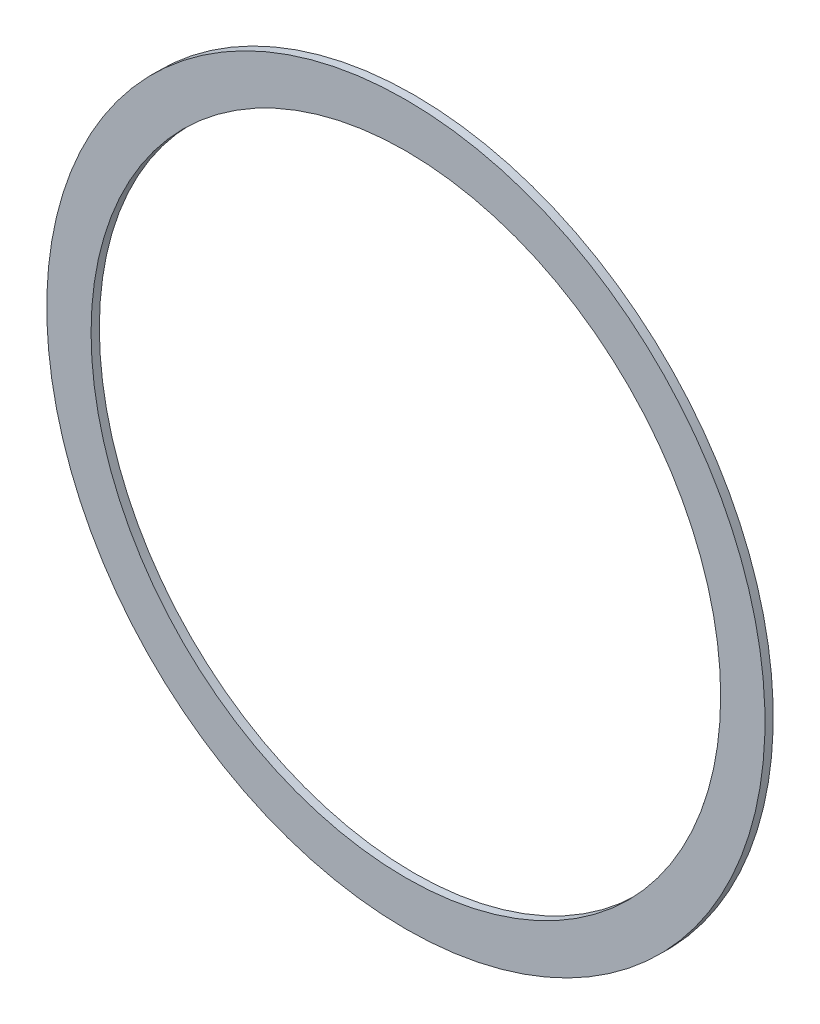
SolidWorks part; units mm, degrees
material "Balsa"
ref_plane "Front Plane" through (0, 0, 0) normal (0, 0, 1) x (1, 0, 0)
ref_plane "Top Plane" through (0, 0, 0) normal (0, 1, 0) x (1, 0, 0)
ref_plane "Right Plane" through (0, 0, 0) normal (1, 0, 0) x (0, 0, -1)
sketch "Sketch1" plane through (0, 0, 0) normal (0, 0, 1) x (1, 0, 0)
  line L0 (0, 0) -> (0, 499.9473) construction
  line L1 (0, -114.7984) -> (0, -129.4545) construction
  line L2 (0, -374.4718) -> (0, 404.2655) construction
  line L3 (-1.651, 142.9921) -> (-1.651, 150.6121) construction
  line L4 (1.651, 142.9921) -> (1.651, 150.6121) construction
  line L5 (-1.651, 142.9921) -> (1.651, 142.9921) construction
  line L6 (136.2041, -53.806) -> (0.0002, 24.7625) construction
  line L7 (-136.2076, -53.7991) -> (0.0002, 24.7625) construction
  line L8 (136.2041, -53.806) -> (0.0002, 24.7625) construction
  line L9 (-136.2076, -53.7991) -> (0.0002, 24.7625) construction
  line L10 (-125.0584, -45.4626) -> (-118.4576, -41.6554) construction
  line L11 (-123.6259, -48.4483) -> (-116.8078, -44.5157) construction
  line L12 (-118.4576, -41.6554) -> (-116.8078, -44.5157) construction
  line L13 (-124.1455, -48.7479) -> (-123.6847, -48.4822) construction
  line L14 (-123.6847, -48.4822) -> (-123.6259, -48.4483) construction
  line L15 (-125.7952, -45.8876) -> (-125.1113, -45.4931) construction
  line L16 (-125.1113, -45.4931) -> (-125.0584, -45.4626) construction
  line L17 (125.4797, -45.7137) -> (125.1075, -45.499) construction
  line L18 (123.8298, -48.5739) -> (123.6807, -48.488) construction
  line L19 (117.0223, -44.647) -> (118.6722, -41.7868) construction
  line L20 (123.6807, -48.488) -> (123.6228, -48.4545) construction
  line L21 (123.6228, -48.4545) -> (117.0223, -44.647) construction
  line L22 (125.1075, -45.499) -> (125.0554, -45.4689) construction
  line L23 (125.0554, -45.4689) -> (118.6722, -41.7868) construction
  line L24 (-115.3206, -47.981) -> (-121.8597, -51.7592)
  line L25 (-113.7312, -50.732) -> (-120.2754, -54.5131)
  line L26 (-113.7312, -50.732) -> (-120.2754, -54.5131) construction
  line L27 (-115.3206, -47.981) -> (-121.8597, -51.7592) construction
  line L28 (-115.4206, -47.9666) -> (-121.9445, -51.7361) construction
  line L29 (-120.2754, -54.5131) -> (-115.3206, -47.981) construction
  line L30 (-117.798, -51.2471) -> (-122.1124, -53.7399) construction
  line L31 (-113.7686, -50.8257) -> (-120.3665, -54.6379) construction
  line L32 (-115.4206, -47.9666) -> (-113.7686, -50.8257) construction
  line L33 (113.7316, -50.7396) -> (129.9098, -60.0883)
  line L34 (115.3212, -47.9888) -> (131.505, -57.3407)
  line L35 (129.9098, -60.0883) -> (131.505, -57.3407)
  line L36 (129.9098, -60.0883) -> (131.505, -57.3407) construction
  line L37 (115.3212, -47.9888) -> (131.505, -57.3407) construction
  line L38 (113.7316, -50.7396) -> (129.9098, -60.0883) construction
  line L39 (129.9098, -60.0883) -> (115.3212, -47.9888) construction
  line L40 (122.6155, -54.0385) -> (101.8722, -42.0519) construction
  line L41 (120.3631, -54.6438) -> (113.7655, -50.8313)
  line L42 (122.0152, -51.7848) -> (122.0057, -51.7794) construction
  line L43 (113.7655, -50.8313) -> (115.4176, -47.9723)
  line L44 (122.0057, -51.7794) -> (121.9413, -51.7421) construction
  line L45 (121.9413, -51.7421) -> (115.4176, -47.9723)
  line L48 (-115.3206, -47.981) -> (-113.7312, -50.732)
  line L49 (-115.3206, -47.981) -> (-113.7312, -50.732) construction
  line L51 (113.7316, -50.7396) -> (115.3212, -47.9888)
  line L52 (113.7316, -50.7396) -> (115.3212, -47.9888) construction
  arc A0 (-1.651, 150.6121) -> (-125.0584, -45.4626) centre (0, 12.7) ccw
  circle A1 centre (0, 12.7) radius 120.904
  arc A2 (0, 150.622) -> (-1.651, 150.6121) centre (0, 12.7) ccw
  circle A3 centre (0, 12.7) radius 137.922 construction
  arc A4 (1.651, 150.6121) -> (0, 150.622) centre (0, 12.7) ccw
  arc A5 (-124.3508, -46.9604) -> (-123.6259, -48.4483) centre (0, 12.7) ccw
  arc A6 (-123.6259, -48.4483) -> (-121.9445, -51.7361) centre (0, 12.7) ccw
  arc A7 (-125.0584, -45.4626) -> (-124.3508, -46.9604) centre (0, 12.7) ccw
  arc A8 (124.3477, -46.9667) -> (125.0554, -45.4689) centre (0, 12.7) ccw
  arc A9 (125.0554, -45.4689) -> (1.651, 150.6121) centre (0, 12.7) ccw
  arc A10 (123.6228, -48.4545) -> (124.3477, -46.9667) centre (0, 12.7) ccw
  arc A11 (-121.9153, -51.7914) -> (-121.1641, -53.1919) centre (0, 12.7) ccw
  arc A12 (-120.3665, -54.6379) -> (120.3631, -54.6438) centre (0, 12.7) ccw
  arc A13 (-121.9445, -51.7361) -> (-121.9153, -51.7914) centre (0, 12.7) ccw
  arc A14 (-121.1641, -53.1919) -> (-120.368, -54.6352) centre (0, 12.7) ccw
  arc A15 (-120.368, -54.6352) -> (-120.397, -54.5834) centre (0, 12.7) ccw construction
  arc A16 (-120.397, -54.5834) -> (-120.3665, -54.6379) centre (0, 12.7) ccw construction
  arc A17 (120.3936, -54.5893) -> (121.2977, -52.9456) centre (0, 12.7) ccw construction
  arc A18 (121.9413, -51.7421) -> (123.6228, -48.4545) centre (0, 12.7) ccw
  arc A19 (120.3631, -54.6438) -> (120.3936, -54.5893) centre (0, 12.7) ccw construction
  arc A20 (121.2977, -52.9456) -> (121.9121, -51.7974) centre (0, 12.7) ccw construction
  arc A21 (121.9121, -51.7974) -> (121.9413, -51.7421) centre (0, 12.7) ccw construction
  spline S1 degree 3 poles (-66.0123, 133.6164) (-70.0128, 131.4329) (-73.8716, 129.0699) (-81.3156, 123.9975) (-84.9009, 121.288) (-91.7995, 115.5249) (-95.113, 112.4712) (-99.0811, 108.4341) (-99.866, 107.6157) (-101.4182, 105.9565) (-102.1865, 105.1147) (-104.4569, 102.5643) (-105.9223, 100.8334) (-110.1768, 95.5512) (-115.4725, 88.2691) (-120.0285, 80.5179) (-123.1654, 74.5269) (-124.1643, 72.5002) (-125.5914, 69.415) (-126.0551, 68.3791) (-126.9587, 66.292) (-127.3989, 65.2397) (-129.5278, 59.9684) (-131.0098, 55.7) (-133.5456, 47.0638) (-134.5993, 42.696) (-136.2795, 33.8613) (-136.906, 29.3944) (-137.415, 23.7472) (-137.5031, 22.6146) (-137.6514, 20.3429) (-137.7116, 19.2049) (-137.8496, 15.7999) (-137.8852, 13.5361) (-137.8263, 6.7629) (-137.3062, -2.2197) (-135.9163, -11.1068) (-134.5433, -17.7359) (-134.0304, -19.9395) (-132.8922, -24.3345) (-132.2653, -26.5303) (-130.2347, -33.03) (-128.6774, -37.2656) (-126.1245, -43.2881) (-125.286, -45.1501) (-124.4066, -46.9926) knots 0 0 0 0 0.03125 0.03125 0.0625 0.0625 0.09375 0.09375 0.101563 0.101563 0.109375 0.109375 0.125 0.125 0.15625 0.1875 0.1875 0.203125 0.203125 0.210938 0.210938 0.21875 0.21875 0.25 0.25 0.28125 0.28125 0.3125 0.3125 0.320313 0.320313 0.328125 0.328125 0.34375 0.34375 0.375 0.40625 0.40625 0.421875 0.421875 0.4375 0.4375 0.46875 0.46875 0.48295 0.48295 0.48295 0.48295 construction
  spline S2 degree 3 poles (-1557.5256, 1030.3086) (-495.2142, -0.1753) (-82.1366, -210.7146) (81.4542, -98.9353) (85.033, -96.2237) (91.9188, -90.4573) (95.2258, -87.4025) (99.1858, -83.3647) (99.9691, -82.5461) (101.5182, -80.8868) (102.2849, -80.0449) (104.5506, -77.4941) (106.013, -75.7632) (110.2586, -70.4809) (112.9006, -66.8403) (117.8152, -59.3254) (120.0877, -55.4512) (123.2166, -49.4629) (124.2129, -47.4373) (125.6361, -44.3538) (126.0986, -43.3185) (126.9997, -41.2327) (127.4386, -40.181) (129.5618, -34.9121) (131.0396, -30.646) (133.5674, -22.0152) (134.6173, -17.6505) (136.2906, -8.8227) (136.914, -4.3596) (137.4197, 1.2823) (137.5071, 2.4139) (137.6542, 4.6834) (137.7138, 5.8206) (137.85, 9.2232) (137.8846, 11.4853) (137.8228, 18.2533) (137.2995, 27.2283) (135.9081, 36.1069) (134.5347, 42.7292) (134.0218, 44.9305) (132.8839, 49.3207) (132.2571, 51.5145) (130.2267, 58.0093) (128.67, 62.2416) (125.1615, 70.5162) (123.2097, 74.5586) (118.9108, 82.4534) (116.5637, 86.3058) (113.3753, 90.999) (112.7241, 91.9325) (111.3996, 93.7822) (110.7272, 94.697) (108.6802, 97.4113) (107.2757, 99.181) (102.9447, 104.3725) (96.8571, 110.9816) (90.1513, 116.9722) (84.8861, 121.2292) (83.0917, 122.6088) (80.3399, 124.6181) (79.4113, 125.2786) (77.543, 126.5731) (76.6028, 127.2075) (71.8708, 130.3161) (67.9881, 132.6004) (60.0328, 136.7739) (55.9603, 138.6631) (47.6249, 142.0446) (43.3619, 143.537) (37.9102, 145.1462) (36.8136, 145.4551) (34.6205, 146.0438) (33.5224, 146.3241) (30.2234, 147.1229) (28.0179, 147.5997) (21.3832, 148.8649) (16.9358, 149.4889) (7.993, 150.3014) (3.4975, 150.4899) (-3.2824, 150.4396) (-5.5486, 150.3672) (-10.0934, 150.1088) (-12.3559, 149.9236) (-19.101, 149.2046) (-23.5473, 148.5072) (-32.3412, 146.6856) (-36.6887, 145.5614) (-43.1354, 143.5526) (-45.2718, 142.8291) (-49.5193, 141.273) (-51.6323, 140.4395) (-274.1905, 46.1884) (-224.836, -608.7963) (101.1574, -1839.6029) knots -1.31339 -1.31339 -1.31339 -1.31339 0.03125 0.03125 0.0625 0.0625 0.09375 0.09375 0.101563 0.101563 0.109375 0.109375 0.125 0.125 0.15625 0.15625 0.1875 0.1875 0.203125 0.203125 0.210938 0.210938 0.21875 0.21875 0.25 0.25 0.28125 0.28125 0.3125 0.3125 0.320313 0.320313 0.328125 0.328125 0.34375 0.34375 0.375 0.40625 0.40625 0.421875 0.421875 0.4375 0.4375 0.46875 0.46875 0.5 0.5 0.53125 0.53125 0.539062 0.539062 0.546875 0.546875 0.5625 0.5625 0.59375 0.625 0.625 0.640625 0.640625 0.648437 0.648437 0.65625 0.65625 0.6875 0.6875 0.71875 0.71875 0.75 0.75 0.757812 0.757812 0.765625 0.765625 0.78125 0.78125 0.8125 0.8125 0.84375 0.84375 0.859375 0.859375 0.875 0.875 0.90625 0.90625 0.9375 0.9375 0.953125 0.953125 0.96875 0.96875 2.612134 2.612134 2.612134 2.612134 only from (66.1767, -108.566) to (-66.0123, 133.6164)
  spline S3 degree 3 poles (66.1767, -108.566) (70.1708, -106.3789) (74.0231, -104.0129) (81.4542, -98.9353) (85.033, -96.2237) (91.9188, -90.4573) (95.2258, -87.4025) (99.1858, -83.3647) (99.9691, -82.5461) (101.5182, -80.8868) (102.2849, -80.0449) (104.5506, -77.4941) (106.013, -75.7632) (110.2586, -70.4809) (112.9006, -66.8403) (117.8152, -59.3254) (120.0877, -55.4512) (123.2166, -49.4629) (124.2129, -47.4373) (125.6361, -44.3538) (126.0986, -43.3185) (126.9997, -41.2327) (127.4386, -40.181) (129.5618, -34.9121) (131.0396, -30.646) (133.5674, -22.0152) (134.6173, -17.6505) (136.2906, -8.8227) (136.914, -4.3596) (137.4197, 1.2823) (137.5071, 2.4139) (137.6542, 4.6834) (137.7138, 5.8206) (137.85, 9.2232) (137.8846, 11.4853) (137.8228, 18.2533) (137.2995, 27.2283) (135.9081, 36.1069) (134.5347, 42.7292) (134.0218, 44.9305) (132.8839, 49.3207) (132.2571, 51.5145) (130.2267, 58.0093) (128.67, 62.2416) (125.1615, 70.5162) (123.2097, 74.5586) (118.9108, 82.4534) (116.5637, 86.3058) (113.3753, 90.999) (112.7241, 91.9325) (111.3996, 93.7822) (110.7272, 94.697) (108.6802, 97.4113) (107.2757, 99.181) (102.9447, 104.3725) (96.8571, 110.9816) (90.1513, 116.9722) (84.8861, 121.2292) (83.0917, 122.6088) (80.3399, 124.6181) (79.4113, 125.2786) (77.543, 126.5731) (76.6028, 127.2075) (71.8708, 130.3161) (67.9881, 132.6004) (60.0328, 136.7739) (55.9603, 138.6631) (47.6249, 142.0446) (43.3619, 143.537) (37.9102, 145.1462) (36.8136, 145.4551) (34.6205, 146.0438) (33.5224, 146.3241) (30.2234, 147.1229) (28.0179, 147.5997) (21.3832, 148.8649) (16.9358, 149.4889) (7.993, 150.3014) (3.4975, 150.4899) (-3.2824, 150.4396) (-5.5486, 150.3672) (-10.0934, 150.1088) (-12.3559, 149.9236) (-19.101, 149.2046) (-23.5473, 148.5072) (-32.3412, 146.6856) (-36.6887, 145.5614) (-43.1354, 143.5526) (-45.2718, 142.8291) (-49.5193, 141.273) (-51.6323, 140.4395) (-57.9206, 137.7764) (-62.0153, 135.798) (-66.0123, 133.6164) knots 0 0 0 0 0.03125 0.03125 0.0625 0.0625 0.09375 0.09375 0.101563 0.101563 0.109375 0.109375 0.125 0.125 0.15625 0.15625 0.1875 0.1875 0.203125 0.203125 0.210938 0.210938 0.21875 0.21875 0.25 0.25 0.28125 0.28125 0.3125 0.3125 0.320313 0.320313 0.328125 0.328125 0.34375 0.34375 0.375 0.40625 0.40625 0.421875 0.421875 0.4375 0.4375 0.46875 0.46875 0.5 0.5 0.53125 0.53125 0.539062 0.539062 0.546875 0.546875 0.5625 0.5625 0.59375 0.625 0.625 0.640625 0.640625 0.648437 0.648437 0.65625 0.65625 0.6875 0.6875 0.71875 0.71875 0.75 0.75 0.757812 0.757812 0.765625 0.765625 0.78125 0.78125 0.8125 0.8125 0.84375 0.84375 0.859375 0.859375 0.875 0.875 0.90625 0.90625 0.9375 0.9375 0.953125 0.953125 0.96875 0.96875 1 1 1 1 construction
  spline S4 degree 3 poles (-124.4066, -46.9926) (-124.169, -47.4906) (-123.9283, -47.9871) (-123.6847, -48.4822) knots 0.48295 0.48295 0.48295 0.48295 0.486788 0.486788 0.486788 0.486788 construction
  spline S5 degree 3 poles (-123.6847, -48.4822) (-122.846, -50.1865) (-121.9718, -51.874) (-118.9108, -57.4955) (-116.5612, -61.3517) (-113.369, -66.0497) (-112.7169, -66.9844) (-111.3913, -68.8351) (-110.7184, -69.7503) (-108.6697, -72.4662) (-107.264, -74.2369) (-102.929, -79.4315) (-96.8353, -86.0447) (-90.1214, -92.0392) (-84.8493, -96.299) (-83.0524, -97.6795) (-80.2967, -99.6899) (-79.367, -100.3507) (-77.4971, -101.6451) (-76.5559, -102.2795) (-71.8198, -105.3881) (-67.9332, -107.6723) (-59.9695, -111.8452) (-55.8924, -113.7339) (-47.5468, -117.114) (-43.2782, -118.6053) (-37.8188, -120.2127) (-36.7216, -120.521) (-34.5268, -121.1085) (-33.4279, -121.3881) (-30.1264, -122.185) (-27.9191, -122.6605) (-21.2788, -123.9216) (-16.8274, -124.5426) (-7.8757, -125.3484) (-3.3755, -125.5332) (3.4122, -125.4766) (5.6812, -125.4019) (10.231, -125.1387) (12.493, -124.9512) (19.2413, -124.2249) (23.6899, -123.5224) (32.4889, -121.6898) (36.8393, -120.5597) (43.2904, -118.5412) (45.4283, -117.8143) (48.6163, -116.6419) (49.6759, -116.2374) (51.7885, -115.4006) (52.8426, -114.968) (58.0839, -112.7404) (62.1792, -110.755) (66.1767, -108.566) knots 0.486788 0.486788 0.486788 0.486788 0.5 0.5 0.53125 0.53125 0.539062 0.539062 0.546875 0.546875 0.5625 0.5625 0.59375 0.625 0.625 0.640625 0.640625 0.648437 0.648437 0.65625 0.65625 0.6875 0.6875 0.71875 0.71875 0.75 0.75 0.757812 0.757812 0.765625 0.765625 0.78125 0.78125 0.8125 0.8125 0.84375 0.84375 0.859375 0.859375 0.875 0.875 0.90625 0.90625 0.9375 0.9375 0.953125 0.953125 0.960937 0.960937 0.96875 0.96875 1 1 1 1 construction
  spline S6 degree 3 poles (-2106.0787, 3411.0956) (-795.1258, 1114.0107) (536.096, -1200.0633) (1875.8445, -3510.6921) knots -1262.072517 -1262.072517 -1262.072517 -1262.072517 1256.953485 1256.953485 1256.953485 1256.953485 weights 1.002223 0.999266 0.999259 1.002202 only from (-121.8597, -51.7592) to (-120.2754, -54.5131)
  spline S7 degree 3 poles (-121.0676, -53.1362) (-120.8035, -53.5952) (-120.5395, -54.0542) (-120.2754, -54.5131) knots 0.5 0.5 0.5 0.5 1 1 1 1 weights 1 1 1 1 construction
  spline S9 degree 3 poles (-121.8597, -51.7592) (-121.5957, -52.2182) (-121.3316, -52.6772) (-121.0676, -53.1362) knots 0 0 0 0 0.5 0.5 0.5 0.5 weights 1 1 1 1 construction
  point P7 (0, -125.5003)
  point P8 (0, 150.4602)
  point P25 (-125.0584, -45.4626)
  point P38 (123.6228, -48.4545)
  point P74 (0, 0)
  dimension "D2" = 275.844
  dimension "D1" = 275.9605
  dimension "D3" = 12.7
  dimension "D5" = 3.302
  dimension "D6" = 7.62
  dimension "D7" = 3.302
  dimension "D8" = 7.62
  dimension "D9" = 3.302
  dimension "D10" = 7.62
  dimension "D11" = 3.302
  dimension "D12" = 7.62
  dimension "D13" = 3.302
  dimension "D14" = 7.62
  dimension "D4" = 17.018
extrude "Boss-Extrude1" [suppressed] add sketch "Sketch1" along normal mid plane 3.175
sketch "Sketch2" plane through (248.2736, -245.0135, 0) normal (0, 0, -1) x (0, -1, 0)
  line L3 (-245.0135, 248.2736) -> (-427.6569, 248.2736) construction
  circle A1 centre (-257.7135, 248.2736) radius 137.922
  circle A16 centre (-257.7135, 248.2736) radius 120.904
  dimension "D1" = 12.7
  dimension "D2" = 275.844
  dimension "D3" = 17.018
fillet "Fillet1" [suppressed] radius 1.27
extrude "Boss-Extrude2" add sketch "Sketch2" along normal mid plane 3.175
equation "\"slotwidth\"=0.13"
equation "\"D11@Sketch1\"=\"slotwidth\""
